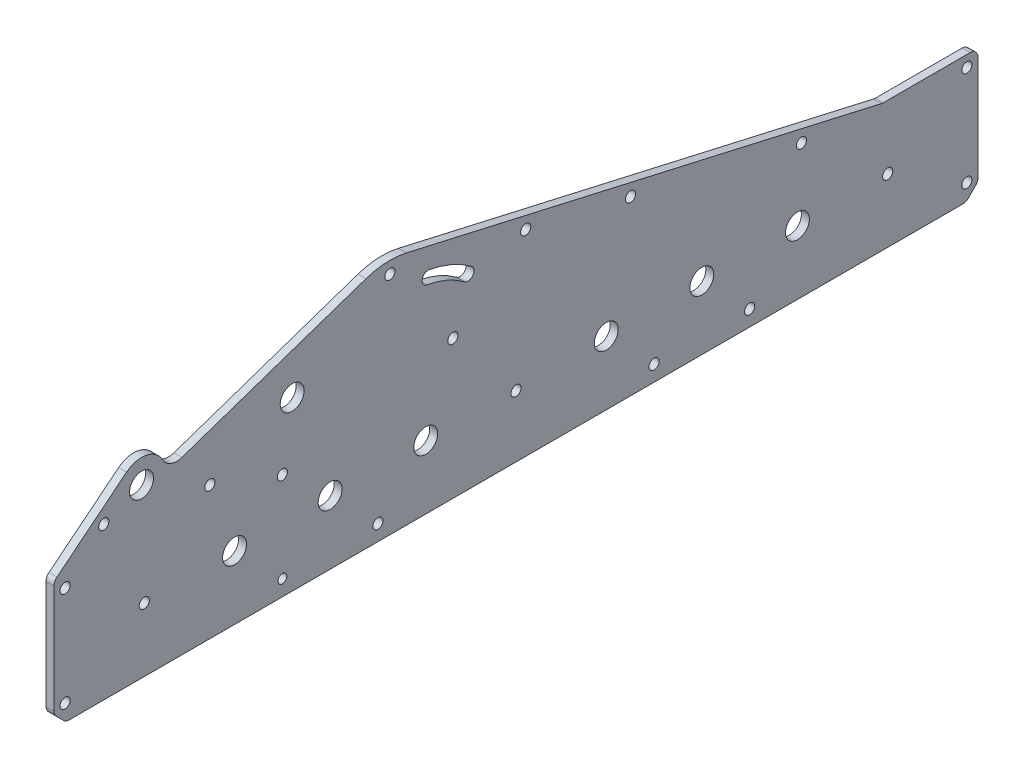
SolidWorks part; units mm, degrees
ref_plane "Front Plane" through (0, 0, 0) normal (0, 0, 1) x (1, 0, 0)
ref_plane "Top Plane" through (0, 0, 0) normal (0, 1, 0) x (1, 0, 0)
ref_plane "Right Plane" through (0, 0, 0) normal (1, 0, 0) x (0, 0, -1)
sketch "Sketch1" plane through (0, 0, 0) normal (1, 0, 0) x (0, 0, -1)
  line L1 (-184.15, -24.6062) -> (184.15, -24.6062)
  line L2 (-184.15, -24.6062) -> (-184.15, 26.1937)
  line L3 (146.05, 26.1937) -> (184.15, 26.1937)
  line L4 (184.15, -24.6062) -> (184.15, 26.1937)
  line L7 (-184.15, 26.1937) -> (-155.196, 49.4899)
  line L9 (146.05, 26.1937) -> (-43.7083, 69.4049)
  line L10 (-59.8122, 68.5626) -> (-133.1862, 43.56)
  arc A0 (-59.8122, 68.5626) -> (-43.7083, 69.4049) centre (-50.2741, 40.5715) cw
  arc A2 (-155.196, 49.4899) -> (-140.8306, 46.5698) centre (-149.225, 42.0687) cw
  arc A4 (-45.783, 38.8051) -> (-54.7652, 42.3379) centre (-50.2741, 40.5715) ccw construction
  arc A5 (-42.7051, 69.1579) -> (-57.8431, 69.1579) centre (-50.2741, 40.5715) ccw construction
  circle A6 centre (-149.225, 42.0687) radius 4.7625 construction
  arc A7 (-140.8306, 46.5698) -> (-133.1862, 43.56) centre (-135.2344, 49.5706) ccw
  point P6 (0, -24.6062)
  dimension "D4" = 9.525
  dimension "D6" = 6.35
  dimension "D1" = 50.8
  dimension "D2" = 368.3
  dimension "D3" = 24.6062
  dimension "D5" = 38.1
extrude "Boss-Extrude1" add sketch "Sketch1" along normal blind 3.175
chamfer "Chamfer1" distance 4.7625 angle 45 2 edges at (1.5875, -24.6062, -184.15) (1.5875, -24.6062, 184.15)
fillet "Fillet1" radius 3.175 7 edges at (1.5875, -24.6062, -179.3875) (1.5875, -19.8437, -184.15) (1.5875, 26.1937, -184.15) (1.5875, -24.6062, 179.3875) (1.5875, -19.8437, 184.15) (1.5875, 26.1937, -146.05) (1.5875, 26.1937, 184.15)
sketch "Sketch4" plane through (3.175, 0, 0) normal (1, 0, 0) x (0, 0, -1)
  circle A2 centre (3.8736, 53.6853) radius 1.905 construction
  circle A3 centre (45.6663, 44.1684) radius 1.905 construction
  circle A4 centre (113.7728, 28.6594) radius 1.905 construction
  circle A5 centre (-25.1593, 30.6938) radius 2.032 construction
  circle A6 centre (-50.2741, 65.3805) radius 1.905 construction
  circle A7 centre (148.1579, 0.7938) radius 2.032 construction
  circle A8 centre (179.705, 21.7488) radius 1.905 construction
  circle A9 centre (179.705, -18.0026) radius 1.905 construction
  circle A11 centre (93.1246, -18.3223) radius 1.905 construction
  circle A12 centre (-164.29, 36.0603) radius 2.032 construction
  arc A13 (-121.6157, 30.4983) -> (-120.4096, 29.7567) centre (-122.0103, 28.5049) ccw construction
  point P3 (0, 0)
  point P9 (55.0246, -18.3223)
  point P11 (-55.0246, -18.3223)
  point P13 (-179.705, 21.7487)
  point P15 (-179.705, -18.0026)
  point P17 (179.705, 21.7488)
  point P19 (148.1579, 0.7938)
  point P21 (-148.1579, 0.7938)
  point P25 (-93.1246, 17.5943)
  point P32 (3.8736, 53.6853)
  point P34 (45.6663, 44.1684)
  point P36 (113.7728, 28.6594)
  point P54 (-25.1593, 30.6938)
  point P59 (-50.2741, 65.3805)
  point P71 (179.705, -18.0026)
  point P76 (93.1246, -18.3223)
  point P85 (-164.29, 36.0603)
  point P87 (-122.0103, 28.5049)
hole_wizard "#8 Clearance Hole1" positions "Sketch4" profile "Sketch5" hole size "#8" standard "ANSI Inch" end condition up to next
sketch "Sketch5" plane through (3.175, 0, 0) normal (0, 1, 0) x (0, 0, -1)
  line L0 (0, 0) -> (0, 3.175)
  line L1 (0, 3.175) -> (2.032, 3.175)
  line L2 (2.032, 3.175) -> (2.032, 0)
  line L5 (2.032, 0) -> (0, 0)
  line L11 (0, -6.35) -> (0, 107.95) construction
  dimension "Thru Hole Dia." = 4.064
  dimension "Thru Hole Depth" = 3.175
sketch "Sketch6" plane through (3.175, 0, 0) normal (1, 0, 0) x (0, 0, -1)
  point P0 (-93.1246, -18.3223)
hole_wizard "#8 Clearance Hole2" positions "Sketch6" profile "Sketch7" hole size "#8" standard "ANSI Inch" end condition up to next
sketch "Sketch7" plane through (3.175, -18.3223, 93.1246) normal (0, 1, 0) x (0, 0, -1)
  line L0 (0, 0) -> (0, 3.175)
  line L1 (0, 3.175) -> (1.778, 3.175)
  line L2 (1.778, 3.175) -> (1.778, 0)
  line L5 (1.778, 0) -> (0, 0)
  line L11 (0, -6.35) -> (0, 107.95) construction
  dimension "Thru Hole Dia." = 3.556
  dimension "Thru Hole Depth" = 3.175
sketch "Sketch8" plane through (3.175, 0, 0) normal (1, 0, 0) x (0, 0, -1)
  circle A0 centre (-89.211, 42.2593) radius 4.7625 construction
  circle A1 centre (35.9746, 0.7937) radius 7.239 construction
  circle A2 centre (-74.0746, 0.7938) radius 7.239 construction
  circle A3 centre (-112.1746, 0.7937) radius 4.7625 construction
  point P0 (-112.1746, 0.7937)
  point P1 (-74.0746, 0.7938)
  point P3 (-35.9746, 0.7938)
  point P5 (35.9746, 0.7937)
  point P7 (74.0746, 0.7937)
  point P9 (112.1746, 0.7937)
  point P13 (-89.211, 42.2593)
hole_wizard "3/8 Clearance Hole1" positions "Sketch8" profile "Sketch9" hole size "3/8" standard "ANSI Inch" end condition up to next
sketch "Sketch9" plane through (3.175, 0.7937, 112.1746) normal (0, 1, 0) x (0, 0, -1)
  line L0 (0, 0) -> (0, 3.175)
  line L1 (0, 3.175) -> (4.7625, 3.175)
  line L2 (4.7625, 3.175) -> (4.7625, 0)
  line L5 (4.7625, 0) -> (0, 0)
  line L11 (0, -6.35) -> (0, 107.95) construction
  dimension "Thru Hole Dia." = 9.525
  dimension "Thru Hole Depth" = 3.175
sketch "Sketch10" plane through (3.175, 0, 0) normal (1, 0, 0) x (0, 0, -1)
  arc A0 (-34.5594, 59.0407) -> (-35.4169, 54.2915) centre (-34.9881, 56.6661) ccw construction
  arc A1 (-20.5473, 47.8719) -> (-35.4169, 54.2915) centre (-41.7582, 19.1724) ccw construction
  arc A2 (-20.5473, 47.8719) -> (-17.6789, 51.753) centre (-19.1131, 49.8125) ccw construction
  arc A3 (-17.6789, 51.753) -> (-34.5594, 59.0407) centre (-41.7582, 19.1724) ccw construction
  arc A4 (-34.5594, 59.0407) -> (-35.4169, 54.2915) centre (-34.9881, 56.6661) ccw
  arc A5 (-20.5473, 47.8719) -> (-35.4169, 54.2915) centre (-41.7582, 19.1724) ccw
  arc A6 (-20.5473, 47.8719) -> (-17.6789, 51.753) centre (-19.1131, 49.8125) ccw
  arc A7 (-17.6789, 51.753) -> (-34.5594, 59.0407) centre (-41.7582, 19.1724) ccw
extrude "Cut-Extrude1" cut sketch "Sketch10" against normal through all
sketch "Sketch11" plane through (3.175, 0, 0) normal (1, 0, 0) x (0, 0, -1)
  circle A0 centre (-149.225, 42.0687) radius 4.7625 construction
  circle A1 centre (-149.225, 42.0687) radius 4.7625
extrude "Cut-Extrude2" cut sketch "Sketch11" against normal through all
